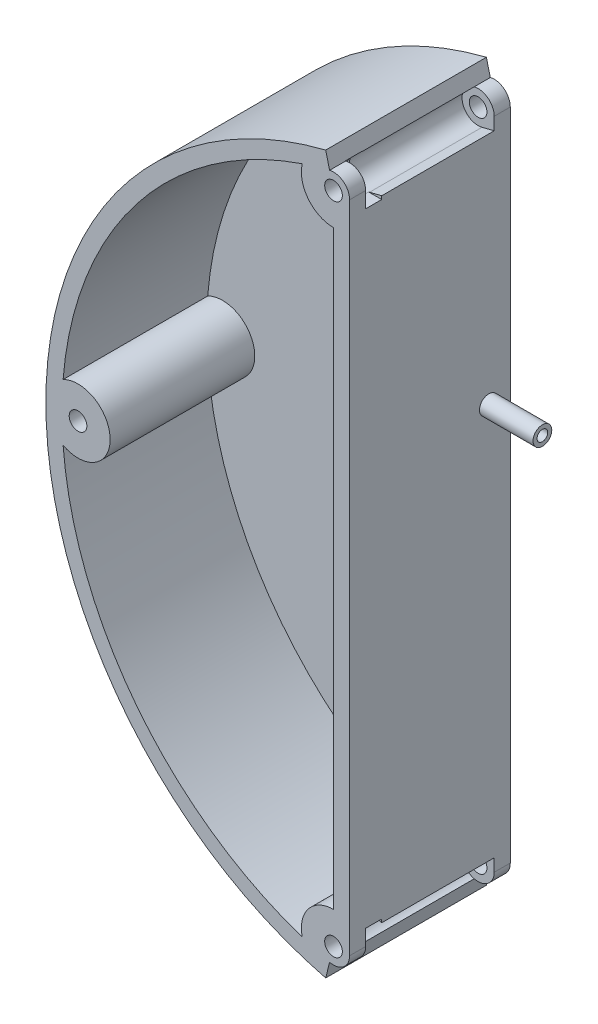
SolidWorks part; units mm, degrees
ref_plane "Front Plane" through (0, 0, 0) normal (0, 0, 1) x (1, 0, 0)
ref_plane "Top Plane" through (0, 0, 0) normal (0, 1, 0) x (1, 0, 0)
ref_plane "Right Plane" through (0, 0, 0) normal (1, 0, 0) x (0, 0, -1)
sketch "Sketch1" plane through (0, 0, 0) normal (0, 0, 1) x (1, 0, 0)
  line L0 (-12.3, -61.1139) -> (-12.3, 61.1139)
  line L1 (-12, -28.4) -> (-12, -52) construction
  line L2 (-16.7571, 66.9343) -> (-16.0286, 64.0241)
  line L4 (-16.7571, -66.9343) -> (-16.0286, -64.0241)
  line L5 (-63, 0) -> (0, 0) construction
  arc A1 (-16.0286, -64.0241) -> (-12.3, -61.1139) centre (-15.3, -61.1139) cw
  circle A2 centre (0, 0) radius 69 construction
  arc A3 (-16.0286, 64.0241) -> (-12.3, 61.1139) centre (-15.3, 61.1139) ccw
  circle A4 centre (-63, 0) radius 3
  arc A6 (-16.7571, 66.9343) -> (-16.7571, -66.9343) centre (0, 0) ccw
  dimension "D2" = 3
  dimension "D6" = 3
  dimension "D8" = 6
  dimension "D1" = 0.3
  dimension "D3" = 3
  dimension "D5" = 3
  dimension "D9" = 63
extrude "Boss-Extrude2" add sketch "Sketch1" along normal blind 30
shell "Shell1" thickness 3 removed face at (-24.7296, 0, 30)
sketch "Sketch3" plane through (-12.3, 0, 0) normal (1, 0, 0) x (0, 1, 0)
  line L0 (-61.1139, 0) -> (61.1139, 0) construction
  circle A0 centre (15, 4) radius 1.75
  dimension "D1" = 3.5
  dimension "D2" = 4
  dimension "D3" = 15
extrude "Boss-Extrude3" add sketch "Sketch3" along normal blind 10
sketch "Sketch5" plane through (0, 0, 0) normal (0, 0, 1) x (1, 0, 0)
  line L0 (-12.3, -61.1139) -> (-12.3, 61.1139)
  line L2 (-16.7571, 66.9343) -> (-16.0286, 64.0241)
  line L4 (-16.7571, -66.9343) -> (-16.0286, -64.0241)
  line L5 (-63, 0) -> (0, 0) construction
  circle A4 centre (-63, 0) radius 1.65
  circle A5 centre (-15.3, 61.1139) radius 1.65
  arc A6 (-16.7571, 66.9343) -> (-16.7571, -66.9343) centre (0, 0) ccw
  arc A7 (-16.0286, 64.0241) -> (-12.3, 61.1139) centre (-15.3, 61.1139) cw
  circle A8 centre (-15.3, -61.1139) radius 1.65
  arc A9 (-12.3, -61.1139) -> (-16.0286, -64.0241) centre (-15.3, -61.1139) cw
  dimension "D2" = 3.3
  dimension "D8" = 3.3
  dimension "D1" = 3.3
  dimension "D3" = 3
  dimension "D5" = 3
extrude "Boss-Extrude4" add sketch "Sketch5" along normal blind 3 contours A4 L0 A7 L2 A6 L4 A9 A8 A5 region at (-36.1775, 0, 0)
sketch "Sketch6" plane through (0, 0, 30) normal (0, 0, 1) x (1, 0, 0)
  line L0 (-63, 3) -> (-68.9348, 3)
  line L1 (-63, -3) -> (-68.9348, -3)
  line L2 (-16.0286, -64.0241) -> (-14.5714, -58.2037) construction
  line L3 (-14.5714, -58.2037) -> (-12.3, -58.7724)
  line L4 (-12.3, -61.1139) -> (-12.3, 61.1139) construction
  line L5 (-12.3, -58.7724) -> (-12.3, -61.1139)
  line L6 (-16.0286, 64.0241) -> (-14.5714, 58.2037) construction
  line L7 (-14.5714, 58.2037) -> (-12.3, 58.7724)
  line L8 (-12.3, 58.7724) -> (-12.3, 61.1139)
  arc A1 (-63, -3) -> (-63, 3) centre (-63, 0) ccw
  arc A2 (-12.3, -61.1139) -> (-14.5714, -58.2037) centre (-15.3, -61.1139) ccw
  arc A3 (-14.5714, 58.2037) -> (-12.3, 61.1139) centre (-15.3, 61.1139) ccw
  arc A4 (-16.7571, 66.9343) -> (-16.7571, -66.9343) centre (0, 0) ccw construction
  arc A5 (-68.9348, 3) -> (-68.9348, -3) centre (-68.9348, 0) ccw
  arc A6 (-12.3, -61.1139) -> (-16.0286, -64.0241) centre (-15.3, -61.1139) ccw construction
  arc A7 (-16.0286, 64.0241) -> (-12.3, 61.1139) centre (-15.3, 61.1139) ccw construction
extrude "Cut-Extrude1" cut sketch "Sketch6" against normal up to surface (27 mm away) up to face at (-61.35, 0, 3)
sketch "Sketch7" plane through (0, 0, 30) normal (0, 0, 1) x (1, 0, 0)
  line L0 (-13.5968, -58.1639) -> (-11.8936, -58.1639)
  line L1 (-11.8936, -61.1139) -> (-13.5968, -58.1639) construction
  line L2 (-13.5968, -58.1639) -> (-17.0032, -58.1639)
  line L3 (-17.0032, -58.1639) -> (-18.7064, -61.1139)
  line L4 (-18.7064, -61.1139) -> (-17.0032, -64.0639)
  line L5 (-17.0032, -64.0639) -> (-13.5968, -64.0639)
  line L6 (-13.5968, -64.0639) -> (-11.8936, -61.1139)
  line L7 (-11.8936, 61.1139) -> (-13.5968, 64.0639)
  line L8 (-13.5968, 64.0639) -> (-17.0032, 64.0639)
  line L9 (-17.0032, 64.0639) -> (-18.7064, 61.1139)
  line L10 (-18.7064, 61.1139) -> (-17.0032, 58.1639)
  line L11 (-17.0032, 58.1639) -> (-13.5968, 58.1639)
  line L12 (-13.5968, 58.1639) -> (-11.8936, 61.1139) construction
  line L13 (-59.5936, 0) -> (-61.2968, 2.95)
  line L14 (-61.2968, 2.95) -> (-64.7032, 2.95)
  line L15 (-64.7032, 2.95) -> (-66.4064, 0)
  line L16 (-66.4064, 0) -> (-64.7032, -2.95)
  line L17 (-64.7032, -2.95) -> (-61.2968, -2.95)
  line L18 (-61.2968, -2.95) -> (-59.5936, 0)
  line L19 (-11.8936, -58.1639) -> (-11.8936, -61.1139)
  line L20 (-13.5968, 58.1639) -> (-11.8936, 58.1639)
  line L21 (-11.8936, 58.1639) -> (-11.8936, 61.1139)
  circle A0 centre (-15.3, -61.1139) radius 2.95 construction
  circle A1 centre (-15.3, 61.1139) radius 2.95 construction
  circle A2 centre (-63, 0) radius 2.95 construction
  dimension "D1" = 5.9
  dimension "D2" = 5.9
  dimension "D3" = 5.9
extrude "Cut-Extrude2" cut sketch "Sketch7" against normal blind 3 from offset 3 offset against normal yes
sketch "Sketch8" plane through (0, 0, 30) normal (0, 0, 1) x (1, 0, 0)
  line L0 (-63, 3) -> (-68.9348, 3)
  line L1 (-68.9348, 3) -> (-68.9348, -3)
  line L2 (-68.9348, -3) -> (-63, -3) construction
  line L3 (-63, -3) -> (-68.9348, -3) construction
  line L4 (-68.9348, -3) -> (-63, -3)
  line L5 (-12.3, -58.7724) -> (-14.5714, -58.2037)
  line L6 (-12.3, -58.7724) -> (-12.3, -61.1139)
  line L7 (-12.3, 61.1139) -> (-12.3, 58.7724)
  line L8 (-14.5714, 58.2037) -> (-12.3, 58.7724)
  circle A0 centre (-63, 0) radius 1.65
  arc A1 (-63, -3) -> (-63, 3) centre (-63, 0) ccw
  circle A2 centre (-15.3, -61.1139) radius 1.65
  arc A3 (-14.5714, -58.2037) -> (-12.3, -61.1139) centre (-15.3, -61.1139) ccw
  circle A4 centre (-15.3, 61.1139) radius 1.65
  arc A5 (-12.3, 61.1139) -> (-14.5714, 58.2037) centre (-15.3, 61.1139) ccw
extrude "Boss-Extrude5" add sketch "Sketch8" against normal blind 3
sketch "Sketch9" plane through (-2.3, 0, 0) normal (1, 0, 0) x (0, 1, 0)
  circle A0 centre (15, 4) radius 1
  dimension "D1" = 2
extrude "Cut-Extrude3" cut sketch "Sketch9" against normal blind 30
